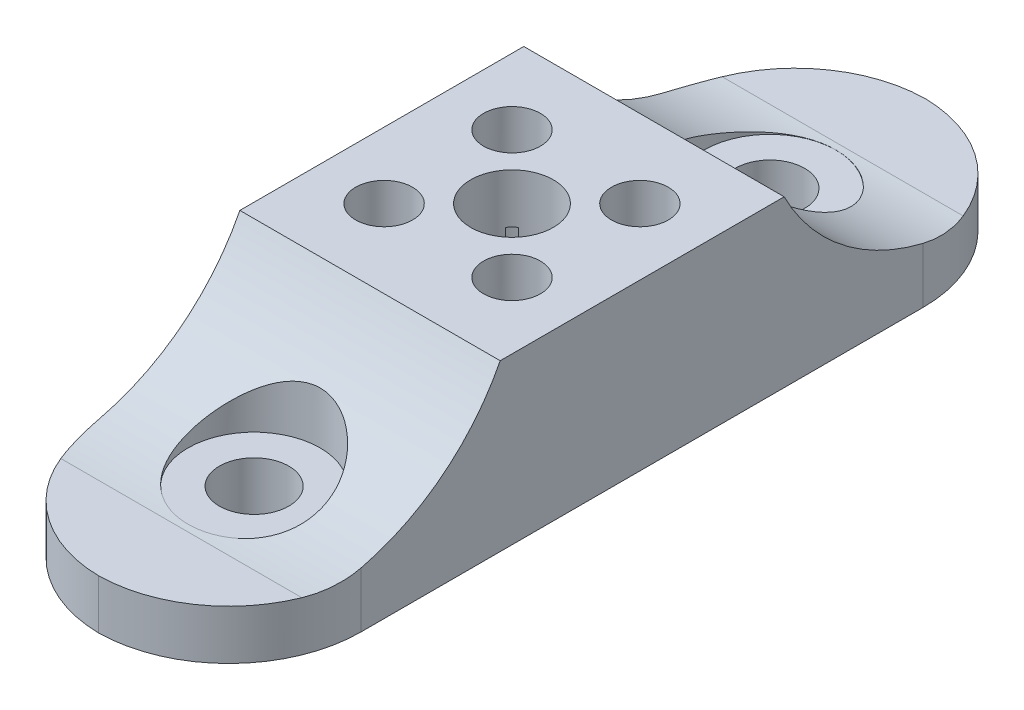
SolidWorks part; units mm, degrees
ref_plane "Front Plane" through (0, 0, 0) normal (0, 0, 1) x (1, 0, 0)
ref_plane "Top Plane" through (0, 0, 0) normal (0, 1, 0) x (1, 0, 0)
ref_plane "Right Plane" through (0, 0, 0) normal (1, 0, 0) x (0, 0, -1)
sketch "Sketch1" plane through (0, 0, 0) normal (0, 1, 0) x (1, 0, 0)
  line L1 (10, 31.75) -> (-10, 31.75)
  line L2 (10, 31.75) -> (10, -31.75)
  line L3 (10, -31.75) -> (-10, -31.75)
  line L4 (-10, 31.75) -> (-10, -31.75)
  line L5 (10, 31.75) -> (-10, -31.75) construction
  line L6 (10, -31.75) -> (-10, 31.75) construction
  point P0 (0, 0)
  dimension "D1" = 20
  dimension "D2" = 63.5
extrude "Boss-Extrude1" add sketch "Sketch1" along normal blind 12.7
sketch "Sketch2" plane through (0, 12.7, 0) normal (0, 1, 0) x (1, 0, 0)
  line L0 (0, 0) -> (0, -31.75) construction
  line L1 (-10, 0) -> (10, 0) construction
  line L2 (-10, 31.75) -> (-10, -31.75) construction
  line L3 (10, -31.75) -> (10, 31.75) construction
  line L4 (-4.9122, 4.9122) -> (4.9122, -4.9122) construction
  line L5 (-10, -31.75) -> (10, -31.75) construction
  line L6 (4.9122, 4.9122) -> (-4.9122, -4.9122) construction
  circle A0 centre (0, 0) radius 3.175
  circle A1 centre (-4.9122, 4.9122) radius 1.6764 construction
  circle A2 centre (4.9122, -4.9122) radius 1.6764 construction
  circle A3 centre (-4.9122, 4.9122) radius 2.1844
  circle A4 centre (4.9122, -4.9122) radius 2.1844
  circle A5 centre (-4.9122, -4.9122) radius 1.6764 construction
  circle A6 centre (4.9122, 4.9122) radius 1.6764 construction
  circle A7 centre (4.9122, 4.9122) radius 2.1844
  circle A8 centre (-4.9122, -4.9122) radius 2.1844
  point P1 (0, 0)
  point P4 (0, 0)
  dimension "D2" = 6.35
  dimension "D3" = 3.3528
  dimension "D4" = 10.541
  dimension "D1" = 45
  dimension "D5" = 0.508
extrude "Cut-Extrude1" cut sketch "Sketch2" against normal through all
sketch "Sketch3" plane through (0, 0, 0) normal (1, 0, 0) x (0, 0, -1)
  line L0 (31.75, 3.81) -> (-31.75, 3.81) construction
  line L1 (31.75, 12.7) -> (31.75, 0) construction
  line L2 (-31.75, 12.7) -> (-31.75, 0) construction
  line L3 (31.75, 0) -> (-31.75, 0) construction
  line L4 (31.75, 12.7) -> (-31.75, 12.7) construction
  line L6 (31.75, 12.7) -> (31.75, 0)
  line L7 (31.75, 12.7) -> (-31.75, 12.7)
  line L8 (0, 12.7) -> (0, 0) construction
  line L9 (31.75, 3.81) -> (25.4, 3.81)
  line L10 (7.0966, 0) -> (7.0966, 12.7) construction
  line L11 (-31.75, 3.81) -> (-25.4, 3.81)
  line L12 (-31.75, 12.7) -> (-31.75, 0)
  arc A0 (25.4, 3.81) -> (10.9066, 12.7) centre (25.4, 20.0693) cw
  arc A1 (-25.4, 3.81) -> (-10.9066, 12.7) centre (-25.4, 20.0693) ccw
  dimension "D1" = 3.81
  dimension "D2" = 3.81
  dimension "D3" = 6.35
extrude "Cut-Extrude2" cut sketch "Sketch3" against normal through all both and the other way through all contours A0 L9 L6 L7 | L11 A1 L7 L12 region at (0, 8.7446, 23.0689) region at (0, 8.7446, -23.0689)
sketch "Sketch4" plane through (0, 0, 0) normal (0, -1, 0) x (1, 0, 0)
  line L0 (0, 31.75) -> (0, -31.75) construction
  line L1 (-10, 31.75) -> (10, 31.75) construction
  line L2 (10, -31.75) -> (-10, -31.75) construction
  circle A0 centre (0, 0) radius 5.334
  circle A1 centre (-4.9122, -4.9122) radius 3.81
  circle A2 centre (4.9122, 4.9122) radius 3.81
  circle A3 centre (-4.9122, 4.9122) radius 3.81
  circle A4 centre (4.9122, -4.9122) radius 3.81
  circle M3 centre (-4.9122, -4.9122) radius 2.1844
  circle M4 centre (4.9122, 4.9122) radius 2.1844
  circle M5 centre (0, 0) radius 3.175
  circle M13 centre (-4.9122, 4.9122) radius 2.1844
  circle M14 centre (4.9122, -4.9122) radius 2.1844
  dimension "D1" = 10.668
  dimension "D2" = 7.62
extrude "Cut-Extrude3" cut sketch "Sketch4" against normal blind 8.89 contours A0 A1 M3 | A0 A1 M3 | A0 M3 | A0 A2 M4 | A0 M4 | A0 A2 M4 | A3 A0 M13 M5 | A3 A0 M13 | A4 A0 M14 M5 | A4 A0 M14 region at (2.952, 0, 2.952) region at (5.0602, 0, 2.0014) region at (7.6327, 0, -2.4009) region at (2.952, 0, -2.952) region at (3.5867, 0, 3.5867) region at (-2.952, 0, 2.952) region at (-2.0014, 0, 5.0602) region at (-7.5302, 0, -7.5302) region at (-2.952, 0, -2.952) region at (-3.5867, 0, -3.5867)
extrude "Cut-Extrude4" cut sketch "Sketch4<3>" against normal blind 3.81 contours A3 A0 M13 M5 | A0 M13 | A3 A0 A1 M5 | A0 A1 M5 M3 | A0 M3 | L0 A0 A4 M5 | L0 A1 A0 M5 | A4 A0 M14 M5 | A0 M14 | A4 A0 A2 M5 | A0 A2 M5 M4 | A0 M4 | L0 A0 A3 M5 | A0 L0 A2 M5 | L0 A4 A2 M5 | L0 A3 A1 M5 region at (0.6716, 0, 4.0685) region at (-0.6716, 0, 4.0685) region at (1.3454, 0, 0) region at (-1.3454, 0, 0) region at (2.952, 0, 2.952) region at (-2.952, 0, 2.952) region at (0.6716, 0, -4.0685) region at (-0.6716, 0, -4.0685) region at (3.5867, 0, 3.5867) region at (-3.5867, 0, 3.5867) region at (-4.0685, 0, 0) region at (-2.952, 0, -2.952) region at (2.952, 0, -2.952) region at (4.0685, 0, 0) region at (-3.5867, 0, -3.5867) region at (3.5867, 0, -3.5867)
sketch "Sketch4<3>" plane through (0, 0, 0) normal (0, -1, 0) x (1, 0, 0) same geometry as "Sketch4"
sketch "Sketch6" plane through (0, 3.81, 0) normal (0, 1, 0) x (1, 0, 0)
  line L0 (0, 31.75) -> (0, 10.9066) construction
  line L1 (-10, 31.75) -> (10, 31.75) construction
  line L2 (-10, 10.9066) -> (10, 10.9066) construction
  line L3 (10, 0) -> (-10, 0) construction
  line L4 (10, -10.9066) -> (10, 10.9066) construction
  line L5 (-10, 10.9066) -> (-10, -10.9066) construction
  line L6 (0, -31.75) -> (0, -10.9066) construction
  circle A0 centre (0, 19.812) radius 2.159 construction
  circle A1 centre (0, 19.812) radius 5.08
  circle A2 centre (0, -19.812) radius 5.08
  circle A3 centre (0, -19.812) radius 2.159 construction
  circle A4 centre (0, -19.812) radius 2.667
  circle A5 centre (0, 19.812) radius 2.667
  dimension "D1" = 4.318
  dimension "D2" = 10.16
  dimension "D3" = 35.306
  dimension "D4" = 5.334
extrude "Cut-Extrude5" cut sketch "Sketch6" along normal up to surface (8.89 mm away) contours A2 A3 | A3 | A1 region at (-4.9363, 3.81, 19.812) up to face at (0, 12.7, 3.175)
extrude "Cut-Extrude6" cut sketch "Sketch6<4>" against normal through all and the other way blind 10 contours A0 | A3 | A5 | A4 region at (0, 3.81, 19.812) region at (0, 3.81, -19.812)
sketch "Sketch6<4>" plane through (0, 3.81, 0) normal (0, 1, 0) x (1, 0, 0) same geometry as "Sketch6"
fillet "Fillet1" radius 10.16 4 edges at (10, 1.905, 31.75) (10, 1.905, -31.75) (-10, 1.905, 31.75) (-10, 1.905, -31.75)
